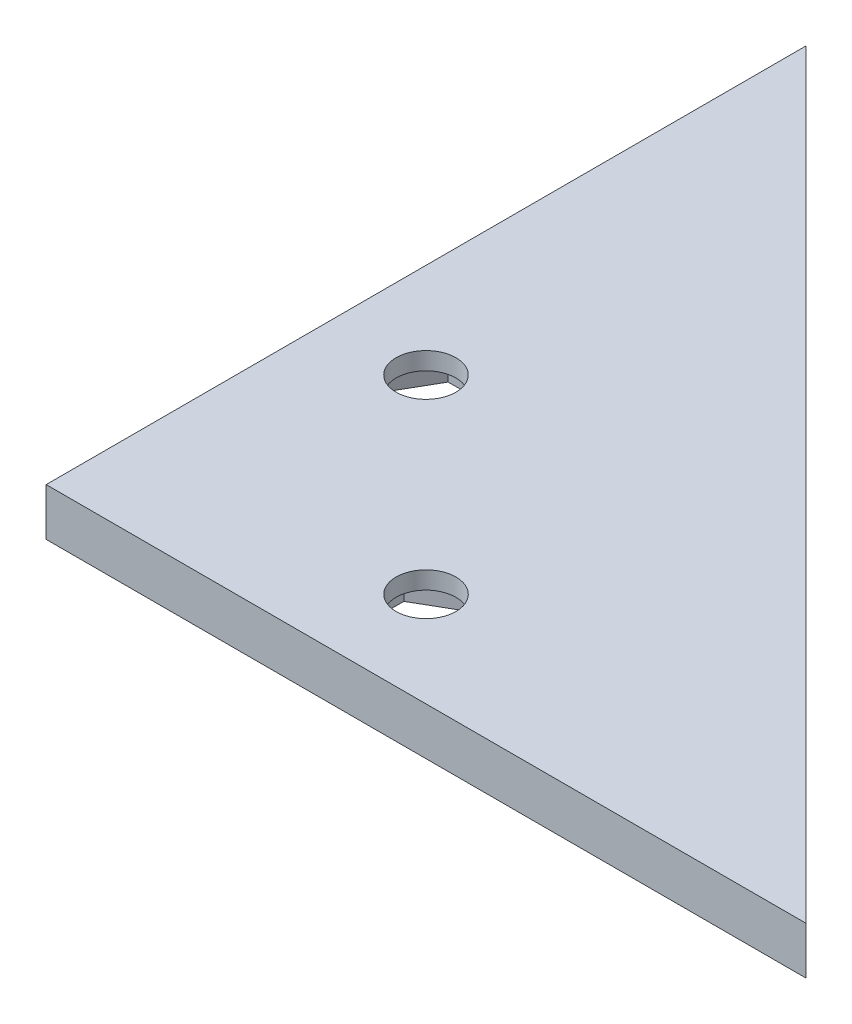
SolidWorks part; units mm, degrees
ref_plane "Front" through (0, 0, 0) normal (0, 0, 1) x (1, 0, 0)
ref_plane "Top" through (0, 0, 0) normal (0, 1, 0) x (1, 0, 0)
ref_plane "Right" through (0, 0, 0) normal (1, 0, 0) x (0, 0, -1)
sketch "Sketch1" plane through (0, 0, 0) normal (0, 1, 0) x (1, 0, 0)
  line L0 (0, 0) -> (50.8, 0)
  line L1 (-21.723, 0) -> (21.723, 0) construction
  line L2 (50.8, 0) -> (0, 50.8)
  line L3 (0, -27.94) -> (0, 27.94) construction
  line L4 (0, 50.8) -> (0, 0)
  dimension "D1" = 50.8
  dimension "D2" = 50.8
extrude "Boss-Extrude1" add sketch "Sketch1" along normal blind 3.175 contours L2 L4 L0
sketch "Sketch2" plane through (0, 3.175, 0) normal (0, 1, 0) x (1, 0, 0)
  line L0 (0, -1.7463) -> (0, 1.7463) construction
  line L1 (-1.7463, 0) -> (1.7463, 0) construction
  line L2 (0, 0) -> (25.4, 25.4) construction
  line L3 (50.8, 0) -> (0, 50.8) construction
  circle A0 centre (19.05, 6.35) radius 2
  circle A1 centre (6.35, 19.05) radius 2
  dimension "D1" = 4
  dimension "D3" = 6.35
  dimension "D2" = 19.05
extrude "Cut-Extrude1" cut sketch "Sketch2" against normal through all contours A0 | A1
sketch "Sketch3" plane through (0, 3.175, 0) normal (0, 1, 0) x (1, 0, 0)
  line L0 (0, 0) -> (25.4, 25.4) construction
  line L1 (8.3707, 15.55) -> (10.3914, 19.05)
  line L2 (10.3914, 19.05) -> (8.3707, 22.55)
  line L3 (0, 0) -> (50.8, 0)
  line L4 (50.8, 0) -> (0, 50.8)
  line L5 (0, 50.8) -> (0, 0)
  line L6 (0, 0) -> (50.8, 0)
  line L7 (50.8, 0) -> (0, 50.8)
  line L8 (0, 50.8) -> (0, 0)
  line L9 (8.3707, 22.55) -> (4.3293, 22.55)
  line L10 (4.3293, 22.55) -> (2.3086, 19.05)
  line L11 (2.3086, 19.05) -> (4.3293, 15.55)
  line L12 (4.3293, 15.55) -> (8.3707, 15.55)
  line L13 (22.55, 4.3293) -> (19.05, 2.3086)
  line L14 (19.05, 2.3086) -> (15.55, 4.3293)
  line L15 (15.55, 4.3293) -> (15.55, 8.3707)
  line L16 (15.55, 8.3707) -> (19.05, 10.3914)
  line L17 (19.05, 10.3914) -> (22.55, 8.3707)
  line L18 (22.55, 8.3707) -> (22.55, 4.3293)
  circle A0 centre (6.35, 19.05) radius 2 construction
  circle A1 centre (6.35, 19.05) radius 2
  circle A2 centre (19.05, 6.35) radius 2 construction
  circle A3 centre (19.05, 6.35) radius 2
  circle A4 centre (6.35, 19.05) radius 3.5 construction
  dimension "D2" = 7
  dimension "D1" = 0
extrude "Cut-Extrude2" cut sketch "Sketch3" along normal blind 2 from surface contours L2 L9 L10 L11 L12 L1 | L17 L18 L13 L14 L15 L16 starting at face at (6.35, 0, -21.05)
